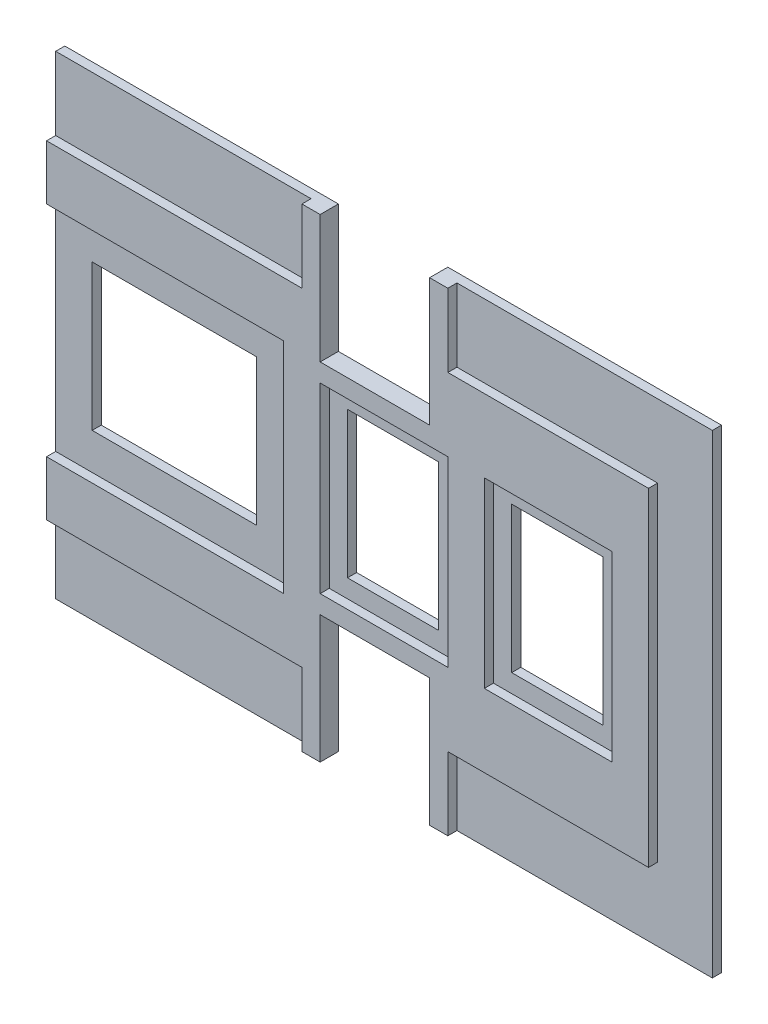
SolidWorks part; units mm, degrees
ref_plane "Front Plane" through (0, 0, 0) normal (0, 0, 1) x (1, 0, 0)
ref_plane "Top Plane" through (0, 0, 0) normal (0, 1, 0) x (1, 0, 0)
ref_plane "Right Plane" through (0, 0, 0) normal (1, 0, 0) x (0, 0, -1)
sketch "Sketch1" plane through (0, 0, 0) normal (0, 0, 1) x (1, 0, 0)
  line L1 (-90, -65) -> (90, -65)
  line L2 (-90, -65) -> (-90, 65)
  line L3 (-90, 65) -> (90, 65)
  line L4 (90, -65) -> (90, 65)
  line L5 (-90, -65) -> (90, 65) construction
  line L6 (-90, 65) -> (90, -65) construction
  point P0 (0, 0)
  dimension "D1" = 180
  dimension "D2" = 130
extrude "Boss-Extrude1" add sketch "Sketch1" along normal blind 5 contours L2 L1 L4 L3
sketch "Sketch2" plane through (0, 0, 5) normal (0, 0, 1) x (1, 0, 0)
  line L0 (0, 84.1786) -> (0, -86.8556) construction
  line L1 (-90, 65) -> (-20, 65)
  line L2 (-90, 65) -> (-90, 45)
  line L3 (-90, 45) -> (-20, 45)
  line L4 (-20, 65) -> (-20, 45)
  line L5 (-121.4818, 0) -> (121.4818, 0) construction
  line L6 (90, 45) -> (20, 45)
  line L7 (20, 65) -> (20, 45)
  line L8 (90, 65) -> (20, 65)
  line L9 (90, 65) -> (90, 45)
  line L10 (90, -65) -> (90, -45)
  line L11 (90, -65) -> (20, -65)
  line L12 (20, -65) -> (20, -45)
  line L13 (90, -45) -> (20, -45)
  line L14 (-90, -45) -> (-20, -45)
  line L15 (-20, -65) -> (-20, -45)
  line L16 (-90, -65) -> (-20, -65)
  line L17 (-90, -65) -> (-90, -45)
  dimension "D1" = 70
  dimension "D2" = 20
extrude "Cut-Extrude1" cut sketch "Sketch2" against normal blind 2.5
sketch "Sketch3" plane through (0, 0, 5) normal (0, 0, 1) x (1, 0, 0)
  line L0 (-90, -45) -> (-90, 45) construction
  line L1 (-90, 30) -> (-25, 30)
  line L2 (-90, 30) -> (-90, -30)
  line L3 (-90, -30) -> (-25, -30)
  line L4 (-25, 30) -> (-25, -30)
  line L5 (-90, 45) -> (-20, 45) construction
  line L6 (-20, -45) -> (-90, -45) construction
  line L8 (20, -25) -> (-15, -25)
  line L9 (20, -25) -> (20, 25)
  line L10 (20, 25) -> (-15, 25)
  line L11 (-15, -25) -> (-15, 25)
  line L12 (20, -25) -> (-15, 25) construction
  line L13 (20, 25) -> (-15, -25) construction
  line L16 (30, -25) -> (65, -25)
  line L17 (30, -25) -> (30, 25)
  line L18 (30, 25) -> (65, 25)
  line L19 (65, -25) -> (65, 25)
  line L20 (30, -25) -> (65, 25) construction
  line L21 (30, 25) -> (65, -25) construction
  point P10 (2.5, 0)
  point P15 (47.5, 0)
  dimension "D1" = 15
  dimension "D2" = 15
  dimension "D3" = 65
  dimension "D4" = 10
  dimension "D5" = 35
  dimension "D6" = 50
  dimension "D7" = 50
  dimension "D8" = 35
  dimension "D9" = 10
extrude "Cut-Extrude2" cut sketch "Sketch3" against normal blind 2.5
sketch "Sketch4" plane through (0, 0, 2.5) normal (0, 0, 1) x (1, 0, 0)
  line L0 (-20, 65) -> (20, 65) construction
  line L1 (-15, 30) -> (15, 30)
  line L2 (-15, 30) -> (-15, 65)
  line L3 (-15, 65) -> (15, 65)
  line L4 (15, 30) -> (15, 65)
  line L5 (-15, 30) -> (15, 65) construction
  line L6 (-15, 65) -> (15, 30) construction
  line L7 (-20, 45) -> (-20, 65) construction
  line L8 (20, 65) -> (20, 45) construction
  line L9 (20, 25) -> (-15, 25) construction
  line L10 (-20, -65) -> (-20, -45) construction
  line L11 (-15, -65) -> (15, -65)
  line L12 (-15, -65) -> (-15, -30)
  line L13 (-15, -30) -> (15, -30)
  line L14 (15, -65) -> (15, -30)
  line L15 (-15, -65) -> (15, -30) construction
  line L16 (-15, -30) -> (15, -65) construction
  line L17 (20, -45) -> (20, -65) construction
  line L18 (-20, -65) -> (20, -65) construction
  line L19 (-15, -25) -> (20, -25) construction
  line L28 (-80, 20) -> (-80, -20)
  line L29 (-80, -20) -> (-35, -20)
  line L30 (-35, -20) -> (-35, 20)
  line L31 (-35, 20) -> (-80, 20)
  line L32 (-80, 20) -> (-80, -20)
  line L33 (-80, -20) -> (-35, -20)
  line L34 (-35, -20) -> (-35, 20)
  line L35 (-35, 20) -> (-80, 20)
  line L40 (60, -20) -> (60, 20)
  line L41 (60, 20) -> (35, 20)
  line L42 (35, 20) -> (35, -20)
  line L43 (35, -20) -> (60, -20)
  line L44 (60, -20) -> (60, 20)
  line L45 (60, 20) -> (35, 20)
  line L46 (35, 20) -> (35, -20)
  line L47 (35, -20) -> (60, -20)
  line L52 (-10, 20) -> (-10, -20)
  line L53 (-10, -20) -> (15, -20)
  line L54 (15, -20) -> (15, 20)
  line L55 (15, 20) -> (-10, 20)
  line L56 (-10, 20) -> (-10, -20)
  line L57 (-10, -20) -> (15, -20)
  line L58 (15, -20) -> (15, 20)
  line L59 (15, 20) -> (-10, 20)
  point P0 (0, 47.5)
  point P13 (0, -47.5)
  dimension "D1" = 5
  dimension "D2" = 5
  dimension "D3" = 5
  dimension "D4" = 5
  dimension "D5" = 5
  dimension "D6" = 5
  dimension "D7" = 10
  dimension "D8" = 5
  dimension "D9" = 5
extrude "Cut-Extrude3" cut sketch "Sketch4" against normal through all and the other way blind 2.5
sketch "Sketch5" plane through (0, 0, 5) normal (0, 0, 1) x (1, 0, 0)
  line L0 (90, -45) -> (20, -45) construction
  line L1 (90, 45) -> (75, 45)
  line L2 (90, 45) -> (90, -45)
  line L3 (90, -45) -> (75, -45)
  line L4 (75, 45) -> (75, -45)
  dimension "D1" = 15
extrude "Cut-Extrude4" cut sketch "Sketch5" against normal blind 2.5
